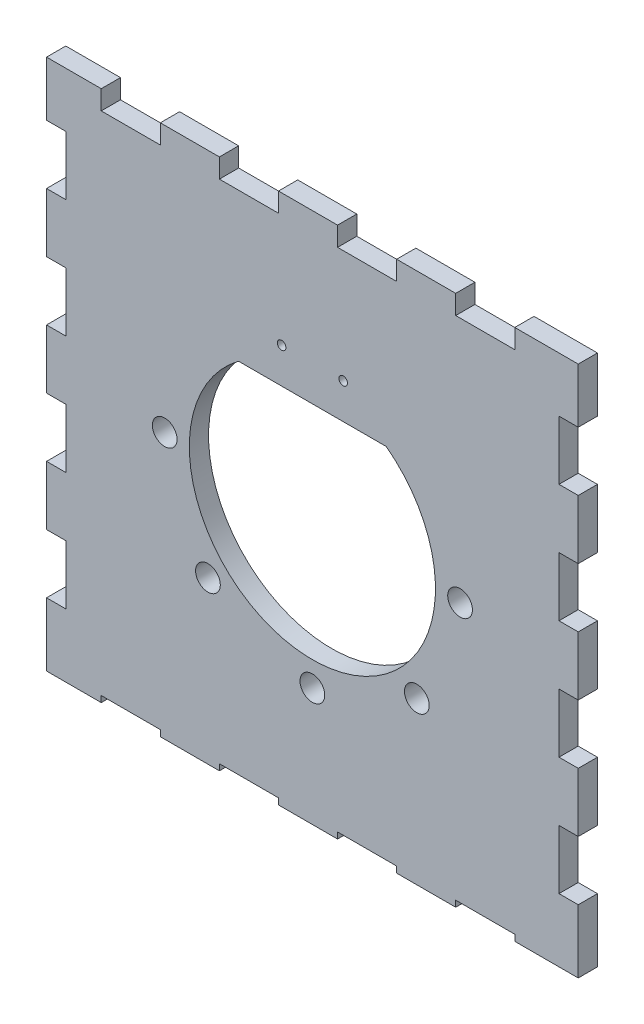
SolidWorks part; units mm, degrees
ref_plane "Front Plane" through (0, 0, 0) normal (0, 0, 1) x (1, 0, 0)
ref_plane "Top Plane" through (0, 0, 0) normal (0, 1, 0) x (1, 0, 0)
ref_plane "Right Plane" through (0, 0, 0) normal (1, 0, 0) x (0, 0, -1)
sketch "Sketch1" plane through (0, 0, 0) normal (0, 0, 1) x (1, 0, 0)
  line L0 (68.58, -68.58) -> (-68.58, 68.58) construction
  line L1 (-68.58, -68.58) -> (68.58, -68.58)
  line L2 (-68.58, -68.58) -> (-68.58, 68.58)
  line L3 (-68.58, 68.58) -> (68.58, 68.58)
  line L4 (68.58, -68.58) -> (68.58, 68.58)
  line L5 (-68.58, -68.58) -> (68.58, 68.58) construction
  point P0 (0, 0)
  dimension "D2" = 137.16
  dimension "D3" = 137.16
extrude "Boss-Extrude1" add sketch "Sketch1" along normal blind 4.9609
sketch "Sketch2" plane through (0, 0, 4.9609) normal (0, 0, 1) x (1, 0, 0)
  line L0 (-19.05, 25.4) -> (19.05, 25.4) construction
  line L1 (0, 25.4) -> (0, 0) construction
  line L2 (-19.05, 25.4) -> (19.05, 25.4)
  circle A0 centre (0, 0) radius 31.75 construction
  arc A1 (-19.05, 25.4) -> (19.05, 25.4) centre (0, 0) ccw
  dimension "D1" = 38.1
  dimension "D2" = 25.4
extrude "Cut-Extrude1" cut sketch "Sketch2" against normal through all
sketch "Sketch4" plane through (0, 0, 4.9609) normal (0, 0, 1) x (1, 0, 0)
  line L0 (-38.1, 0) -> (38.1, 0) construction
  line L1 (0, 0) -> (-26.9408, -26.9408) construction
  line L2 (0, 0) -> (0, -38.1) construction
  line L3 (0, 0) -> (26.9408, -26.9408) construction
  circle A0 centre (0, 0) radius 38.1 construction
  circle A1 centre (-38.1, 0) radius 3.1877
  circle A2 centre (-26.9408, -26.9408) radius 3.1877
  circle A3 centre (0, -38.1) radius 3.1877
  circle A4 centre (26.9408, -26.9408) radius 3.1877
  circle A5 centre (38.1, 0) radius 3.1877
  point P6 (0, 0)
  dimension "D1" = 76.2
  dimension "D4" = 6.3754
  dimension "D2" = 45
  dimension "D3" = 45
extrude "Cut-Extrude2" cut sketch "Sketch4" against normal through all
sketch "Sketch6" plane through (0, 0, 4.9609) normal (0, 0, 1) x (1, 0, 0)
  line L20 (-68.58, 68.58) -> (-68.58, 54.4678) construction
  line L21 (-68.58, 68.58) -> (-68.58, -68.58) construction
  line L22 (-68.58, 23.9878) -> (-68.58, 8.7478)
  line L23 (-68.58, 54.4678) -> (-63.6165, 54.4678)
  line L24 (-68.58, 54.4678) -> (-68.58, 39.2278)
  line L25 (-68.58, 39.2278) -> (-63.6165, 39.2278)
  line L26 (-63.6165, 54.4678) -> (-63.6165, 39.2278)
  line L27 (-68.58, 23.9878) -> (-63.6165, 23.9878)
  line L28 (-63.6165, 23.9878) -> (-63.6165, 8.7478)
  line L29 (-68.58, 8.7478) -> (-63.6165, 8.7478)
  line L30 (-68.58, -6.4922) -> (-68.58, -21.7322)
  line L31 (-68.58, -6.4922) -> (-63.6165, -6.4922)
  line L32 (-63.6165, -6.4922) -> (-63.6165, -21.7322)
  line L33 (-68.58, -21.7322) -> (-63.6165, -21.7322)
  line L34 (-68.58, -36.9722) -> (-68.58, -52.2122)
  line L35 (-68.58, -36.9722) -> (-63.6165, -36.9722)
  line L36 (-63.6165, -36.9722) -> (-63.6165, -52.2122)
  line L37 (-68.58, -52.2122) -> (-63.6165, -52.2122)
  line L38 (-68.58, 68.58) -> (-54.4678, 68.58) construction
  line L39 (-63.6165, 39.2278) -> (-63.6165, 23.9878) construction
  line L60 (68.58, 68.58) -> (-68.58, 68.58) construction
  line L61 (68.58, 68.58) -> (68.58, 54.4678) construction
  line L62 (68.58, -68.58) -> (68.58, 68.58) construction
  line L63 (68.58, 23.9878) -> (68.58, 8.7478)
  line L64 (68.58, 54.4678) -> (63.6165, 54.4678)
  line L65 (68.58, 54.4678) -> (68.58, 39.2278)
  line L66 (68.58, 39.2278) -> (63.6165, 39.2278)
  line L67 (63.6165, 54.4678) -> (63.6165, 39.2278)
  line L68 (68.58, 23.9878) -> (63.6165, 23.9878)
  line L69 (63.6165, 23.9878) -> (63.6165, 8.7478)
  line L70 (68.58, 8.7478) -> (63.6165, 8.7478)
  line L71 (68.58, -6.4922) -> (68.58, -21.7322)
  line L72 (68.58, -6.4922) -> (63.6165, -6.4922)
  line L73 (63.6165, -6.4922) -> (63.6165, -21.7322)
  line L74 (68.58, -21.7322) -> (63.6165, -21.7322)
  line L75 (68.58, -36.9722) -> (68.58, -52.2122)
  line L76 (68.58, -36.9722) -> (63.6165, -36.9722)
  line L77 (63.6165, -36.9722) -> (63.6165, -52.2122)
  line L78 (68.58, -52.2122) -> (63.6165, -52.2122)
  line L79 (63.6165, 39.2278) -> (63.6165, 23.9878) construction
  line L80 (-23.9878, 68.58) -> (-23.9878, 63.6165)
  line L81 (-54.4678, 68.58) -> (-39.2278, 68.58)
  line L82 (-54.4678, 68.58) -> (-54.4678, 63.6165)
  line L83 (-54.4678, 63.6165) -> (-39.2278, 63.6165)
  line L84 (-39.2278, 68.58) -> (-39.2278, 63.6165)
  line L85 (-23.9878, 68.58) -> (-8.7478, 68.58)
  line L86 (-8.7478, 68.58) -> (-8.7478, 63.6165)
  line L87 (-23.9878, 63.6165) -> (-8.7478, 63.6165)
  line L88 (6.4922, 68.58) -> (6.4922, 63.6165)
  line L89 (6.4922, 68.58) -> (21.7322, 68.58)
  line L90 (21.7322, 68.58) -> (21.7322, 63.6165)
  line L91 (6.4922, 63.6165) -> (21.7322, 63.6165)
  line L92 (36.9722, 68.58) -> (36.9722, 63.6165)
  line L93 (36.9722, 68.58) -> (52.2122, 68.58)
  line L94 (52.2122, 68.58) -> (52.2122, 63.6165)
  line L95 (36.9722, 63.6165) -> (52.2122, 63.6165)
  line L96 (-39.2278, 68.58) -> (-23.9878, 68.58) construction
  line L97 (-68.58, -68.58) -> (-54.4678, -68.58) construction
  line L98 (-68.58, -68.58) -> (68.58, -68.58) construction
  line L99 (-23.9878, -68.58) -> (-23.9878, -66.9925)
  line L100 (-54.4678, -68.58) -> (-39.2278, -68.58)
  line L101 (-54.4678, -68.58) -> (-54.4678, -66.9925)
  line L102 (-54.4678, -66.9925) -> (-39.2278, -66.9925)
  line L103 (-39.2278, -68.58) -> (-39.2278, -66.9925)
  line L104 (-23.9878, -68.58) -> (-8.7478, -68.58)
  line L105 (-8.7478, -68.58) -> (-8.7478, -66.9925)
  line L106 (-23.9878, -66.9925) -> (-8.7478, -66.9925)
  line L107 (6.4922, -68.58) -> (6.4922, -66.9925)
  line L108 (6.4922, -68.58) -> (21.7322, -68.58)
  line L109 (21.7322, -68.58) -> (21.7322, -66.9925)
  line L110 (6.4922, -66.9925) -> (21.7322, -66.9925)
  line L111 (36.9722, -68.58) -> (36.9722, -66.9925)
  line L112 (36.9722, -68.58) -> (52.2122, -68.58)
  line L113 (52.2122, -68.58) -> (52.2122, -66.9925)
  line L114 (36.9722, -66.9925) -> (52.2122, -66.9925)
  line L115 (-39.2278, -66.9925) -> (-23.9878, -66.9925) construction
  line L116 (-39.2278, 63.6165) -> (-23.9878, 63.6165) construction
  dimension "D2" = 14.1122
  dimension "D4" = 14.1122
  dimension "D10" = 4
  dimension "D13" = 14.1122
  dimension "D15" = 15.24
  dimension "D16" = 4.9635
  dimension "D18" = 15.24
  dimension "D3" = 1.5875
  dimension "D12" = 14.1122
  dimension "D7" = 4
  dimension "D17" = 4
  dimension "D20" = 4
extrude "Cut-Extrude5" cut sketch "Sketch6" against normal through all
sketch "Sketch7" plane through (0, 0, 4.9609) normal (0, 0, 1) x (1, 0, 0)
  line L0 (19.05, 25.4) -> (-19.05, 25.4) construction
  line L1 (19.05, 25.4) -> (-19.05, 25.4) construction
  line L2 (0, 25.4) -> (0, 34.5275) construction
  line L3 (-7.9375, 34.5275) -> (7.9375, 34.5275) construction
  line L68 (-63.6165, 54.4678) -> (-63.6165, 39.2278)
  line L69 (-63.6165, 39.2278) -> (-68.58, 39.2278)
  line L70 (-68.58, 39.2278) -> (-68.58, 23.9878)
  line L71 (-68.58, 23.9878) -> (-63.6165, 23.9878)
  line L72 (-63.6165, 23.9878) -> (-63.6165, 8.7478)
  line L73 (-63.6165, 8.7478) -> (-68.58, 8.7478)
  line L74 (-68.58, 8.7478) -> (-68.58, -6.4922)
  line L75 (-68.58, -6.4922) -> (-63.6165, -6.4922)
  line L76 (-63.6165, -6.4922) -> (-63.6165, -21.7322)
  line L77 (-63.6165, -21.7322) -> (-68.58, -21.7322)
  line L78 (-68.58, -21.7322) -> (-68.58, -36.9722)
  line L79 (-68.58, -36.9722) -> (-63.6165, -36.9722)
  line L80 (-63.6165, -36.9722) -> (-63.6165, -52.2122)
  line L81 (-63.6165, -52.2122) -> (-68.58, -52.2122)
  line L82 (-68.58, -52.2122) -> (-68.58, -68.58)
  line L83 (-68.58, -68.58) -> (-54.4678, -68.58)
  line L84 (-54.4678, -68.58) -> (-54.4678, -66.9925)
  line L85 (-54.4678, -66.9925) -> (-39.2278, -66.9925)
  line L86 (-39.2278, -66.9925) -> (-39.2278, -68.58)
  line L87 (-39.2278, -68.58) -> (-23.9878, -68.58)
  line L88 (-23.9878, -68.58) -> (-23.9878, -66.9925)
  line L89 (-23.9878, -66.9925) -> (-8.7478, -66.9925)
  line L90 (-8.7478, -66.9925) -> (-8.7478, -68.58)
  line L91 (-8.7478, -68.58) -> (6.4922, -68.58)
  line L92 (6.4922, -68.58) -> (6.4922, -66.9925)
  line L93 (6.4922, -66.9925) -> (21.7322, -66.9925)
  line L94 (21.7322, -66.9925) -> (21.7322, -68.58)
  line L95 (21.7322, -68.58) -> (36.9722, -68.58)
  line L96 (36.9722, -68.58) -> (36.9722, -66.9925)
  line L97 (36.9722, -66.9925) -> (52.2122, -66.9925)
  line L98 (52.2122, -66.9925) -> (52.2122, -68.58)
  line L99 (52.2122, -68.58) -> (68.58, -68.58)
  line L100 (68.58, -68.58) -> (68.58, -52.2122)
  line L101 (68.58, -52.2122) -> (63.6165, -52.2122)
  line L102 (63.6165, -52.2122) -> (63.6165, -36.9722)
  line L103 (63.6165, -36.9722) -> (68.58, -36.9722)
  line L104 (68.58, -36.9722) -> (68.58, -21.7322)
  line L105 (68.58, -21.7322) -> (63.6165, -21.7322)
  line L106 (63.6165, -21.7322) -> (63.6165, -6.4922)
  line L107 (63.6165, -6.4922) -> (68.58, -6.4922)
  line L108 (68.58, -6.4922) -> (68.58, 8.7478)
  line L109 (68.58, 8.7478) -> (63.6165, 8.7478)
  line L110 (63.6165, 8.7478) -> (63.6165, 23.9878)
  line L111 (63.6165, 23.9878) -> (68.58, 23.9878)
  line L112 (68.58, 23.9878) -> (68.58, 39.2278)
  line L113 (68.58, 39.2278) -> (63.6165, 39.2278)
  line L114 (63.6165, 39.2278) -> (63.6165, 54.4678)
  line L115 (63.6165, 54.4678) -> (68.58, 54.4678)
  line L116 (68.58, 54.4678) -> (68.58, 68.58)
  line L117 (68.58, 68.58) -> (52.2122, 68.58)
  line L118 (52.2122, 68.58) -> (52.2122, 63.6165)
  line L119 (52.2122, 63.6165) -> (36.9722, 63.6165)
  line L120 (36.9722, 63.6165) -> (36.9722, 68.58)
  line L121 (36.9722, 68.58) -> (21.7322, 68.58)
  line L122 (21.7322, 68.58) -> (21.7322, 63.6165)
  line L123 (21.7322, 63.6165) -> (6.4922, 63.6165)
  line L124 (6.4922, 63.6165) -> (6.4922, 68.58)
  line L125 (6.4922, 68.58) -> (-8.7478, 68.58)
  line L126 (-8.7478, 68.58) -> (-8.7478, 63.6165)
  line L127 (-8.7478, 63.6165) -> (-23.9878, 63.6165)
  line L128 (-23.9878, 63.6165) -> (-23.9878, 68.58)
  line L129 (-23.9878, 68.58) -> (-39.2278, 68.58)
  line L130 (-39.2278, 68.58) -> (-39.2278, 63.6165)
  line L131 (-39.2278, 63.6165) -> (-54.4678, 63.6165)
  line L132 (-54.4678, 63.6165) -> (-54.4678, 68.58)
  line L133 (-54.4678, 68.58) -> (-68.58, 68.58)
  line L134 (-68.58, 68.58) -> (-68.58, 54.4678)
  line L135 (-68.58, 54.4678) -> (-63.6165, 54.4678)
  line L136 (-63.6165, 54.4678) -> (-63.6165, 39.2278)
  line L137 (-63.6165, 39.2278) -> (-68.58, 39.2278)
  line L138 (-68.58, 39.2278) -> (-68.58, 23.9878)
  line L139 (-68.58, 23.9878) -> (-63.6165, 23.9878)
  line L140 (-63.6165, 23.9878) -> (-63.6165, 8.7478)
  line L141 (-63.6165, 8.7478) -> (-68.58, 8.7478)
  line L142 (-68.58, 8.7478) -> (-68.58, -6.4922)
  line L143 (-68.58, -6.4922) -> (-63.6165, -6.4922)
  line L144 (-63.6165, -6.4922) -> (-63.6165, -21.7322)
  line L145 (-63.6165, -21.7322) -> (-68.58, -21.7322)
  line L146 (-68.58, -21.7322) -> (-68.58, -36.9722)
  line L147 (-68.58, -36.9722) -> (-63.6165, -36.9722)
  line L148 (-63.6165, -36.9722) -> (-63.6165, -52.2122)
  line L149 (-63.6165, -52.2122) -> (-68.58, -52.2122)
  line L150 (-68.58, -52.2122) -> (-68.58, -68.58)
  line L151 (-68.58, -68.58) -> (-54.4678, -68.58)
  line L152 (-54.4678, -68.58) -> (-54.4678, -66.9925)
  line L153 (-54.4678, -66.9925) -> (-39.2278, -66.9925)
  line L154 (-39.2278, -66.9925) -> (-39.2278, -68.58)
  line L155 (-39.2278, -68.58) -> (-23.9878, -68.58)
  line L156 (-23.9878, -68.58) -> (-23.9878, -66.9925)
  line L157 (-23.9878, -66.9925) -> (-8.7478, -66.9925)
  line L158 (-8.7478, -66.9925) -> (-8.7478, -68.58)
  line L159 (-8.7478, -68.58) -> (6.4922, -68.58)
  line L160 (6.4922, -68.58) -> (6.4922, -66.9925)
  line L161 (6.4922, -66.9925) -> (21.7322, -66.9925)
  line L162 (21.7322, -66.9925) -> (21.7322, -68.58)
  line L163 (21.7322, -68.58) -> (36.9722, -68.58)
  line L164 (36.9722, -68.58) -> (36.9722, -66.9925)
  line L165 (36.9722, -66.9925) -> (52.2122, -66.9925)
  line L166 (52.2122, -66.9925) -> (52.2122, -68.58)
  line L167 (52.2122, -68.58) -> (68.58, -68.58)
  line L168 (68.58, -68.58) -> (68.58, -52.2122)
  line L169 (68.58, -52.2122) -> (63.6165, -52.2122)
  line L170 (63.6165, -52.2122) -> (63.6165, -36.9722)
  line L171 (63.6165, -36.9722) -> (68.58, -36.9722)
  line L172 (68.58, -36.9722) -> (68.58, -21.7322)
  line L173 (68.58, -21.7322) -> (63.6165, -21.7322)
  line L174 (63.6165, -21.7322) -> (63.6165, -6.4922)
  line L175 (63.6165, -6.4922) -> (68.58, -6.4922)
  line L176 (68.58, -6.4922) -> (68.58, 8.7478)
  line L177 (68.58, 8.7478) -> (63.6165, 8.7478)
  line L178 (63.6165, 8.7478) -> (63.6165, 23.9878)
  line L179 (63.6165, 23.9878) -> (68.58, 23.9878)
  line L180 (68.58, 23.9878) -> (68.58, 39.2278)
  line L181 (68.58, 39.2278) -> (63.6165, 39.2278)
  line L182 (63.6165, 39.2278) -> (63.6165, 54.4678)
  line L183 (63.6165, 54.4678) -> (68.58, 54.4678)
  line L184 (68.58, 54.4678) -> (68.58, 68.58)
  line L185 (68.58, 68.58) -> (52.2122, 68.58)
  line L186 (52.2122, 68.58) -> (52.2122, 63.6165)
  line L187 (52.2122, 63.6165) -> (36.9722, 63.6165)
  line L188 (36.9722, 63.6165) -> (36.9722, 68.58)
  line L189 (36.9722, 68.58) -> (21.7322, 68.58)
  line L190 (21.7322, 68.58) -> (21.7322, 63.6165)
  line L191 (21.7322, 63.6165) -> (6.4922, 63.6165)
  line L192 (6.4922, 63.6165) -> (6.4922, 68.58)
  line L193 (6.4922, 68.58) -> (-8.7478, 68.58)
  line L194 (-8.7478, 68.58) -> (-8.7478, 63.6165)
  line L195 (-8.7478, 63.6165) -> (-23.9878, 63.6165)
  line L196 (-23.9878, 63.6165) -> (-23.9878, 68.58)
  line L197 (-23.9878, 68.58) -> (-39.2278, 68.58)
  line L198 (-39.2278, 68.58) -> (-39.2278, 63.6165)
  line L199 (-39.2278, 63.6165) -> (-54.4678, 63.6165)
  line L200 (-54.4678, 63.6165) -> (-54.4678, 68.58)
  line L201 (-54.4678, 68.58) -> (-68.58, 68.58)
  line L202 (-68.58, 68.58) -> (-68.58, 54.4678)
  line L203 (-68.58, 54.4678) -> (-63.6165, 54.4678)
  circle A0 centre (-7.9375, 34.5275) radius 1.1049
  circle A1 centre (7.9375, 34.5275) radius 1.1049
  point P16 (0, 34.5275)
  dimension "D4" = 2.2098
  dimension "D2" = 9.1275
  dimension "D3" = 15.875
  dimension "D1" = 0
extrude "Cut-Extrude6" cut sketch "Sketch7" against normal through all flip side to cut
